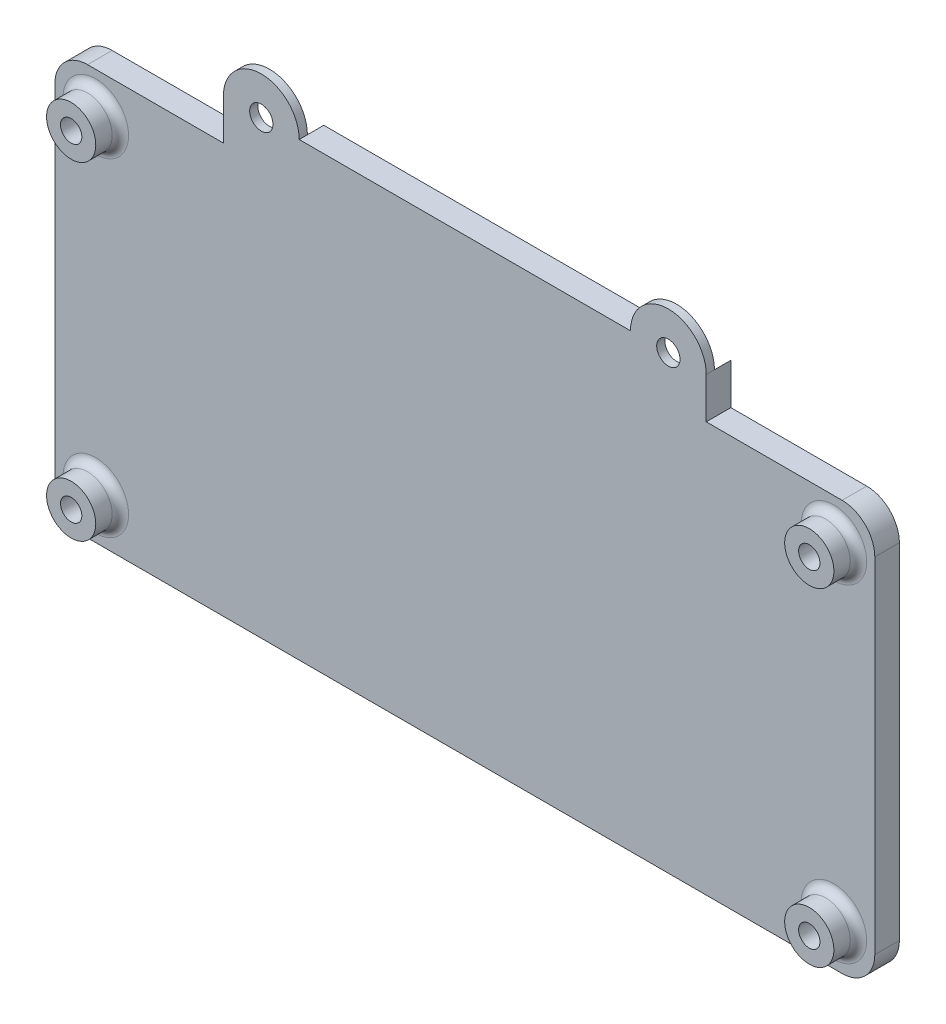
SolidWorks part; units mm, degrees
note: The reader was unsure of these and kept them because the rebuilt part matched: shared geometry of "Sketch1<3>".
ref_plane "Front Plane" through (0, 0, 0) normal (0, 0, 1) x (1, 0, 0)
ref_plane "Top Plane" through (0, 0, 0) normal (0, 1, 0) x (1, 0, 0)
ref_plane "Right Plane" through (0, 0, 0) normal (1, 0, 0) x (0, 0, -1)
sketch "Sketch1" plane through (0, 0, 0) normal (0, 0, 1) x (1, 0, 0)
  line L0 (4, 0.0127) -> (96.0002, 0.0127)
  line L1 (99.9875, 4) -> (99.9875, 46.0001)
  line L2 (96.0002, 49.9874) -> (4, 49.9874)
  line L3 (0.0127, 46.0001) -> (0.0127, 4)
  circle A0 centre (5, 45.0001) radius 1.3
  circle A1 centre (95.0002, 45.0001) radius 1.3
  circle A2 centre (95.0002, 5) radius 1.3
  circle A3 centre (5, 5) radius 1.3
  arc A4 (0.0127, 4) -> (4, 0.0127) centre (4, 4) ccw
  arc A5 (4, 49.9874) -> (0.0127, 46.0001) centre (4, 46.0001) ccw
  arc A6 (96.0002, 49.9874) -> (99.9875, 46.0001) centre (96.0002, 46.0001) cw
  arc A7 (99.9875, 4) -> (96.0002, 0.0127) centre (96.0002, 4) cw
  circle A8 centre (5, 45.0001) radius 3
  circle A9 centre (95.0002, 45.0001) radius 3
  circle A10 centre (5, 5) radius 3
  circle A11 centre (95.0002, 5) radius 3
extrude "Boss-Extrude1" add sketch "Sketch1" along normal blind 3 contours A7 L1 A6 L2 A5 L3 A4 L0 A11 A10 A9 A8
extrude "Boss-Extrude2" add sketch "Sketch1<3>" along normal blind 6 contours A8 A0 | A9 A1 | A11 A2 | A10 A3
sketch "Sketch1<3>" plane through (0, 0, 0) normal (0, 0, 1) x (1, 0, 0) same geometry as "Sketch1"
fillet "Fillet1" radius 1 4 edges at (98.0002, 5, 3) (98.0002, 45.0001, 3) (8, 45.0001, 3) (8, 5, 3)
sketch "Sketch2" plane through (0, 0, 3) normal (0, 0, 1) x (1, 0, 0)
  line L0 (20.5659, 54.9874) -> (20.5895, 61.7526)
  line L1 (20.5895, 61.7526) -> (29.8027, 61.729)
  line L2 (29.8027, 61.729) -> (29.8027, 54.9874)
  line L3 (70.1975, 54.9874) -> (70.1975, 61.729)
  line L4 (70.1975, 61.729) -> (79.4343, 61.729)
  line L5 (79.4343, 61.729) -> (79.4343, 54.9874)
  line L6 (25.1843, 54.9874) -> (74.8159, 54.9874)
  line L7 (20.5659, 54.9874) -> (20.5659, 49.9874)
  line L8 (96.0002, 49.9874) -> (4, 49.9874) construction
  line L9 (20.5659, 49.9874) -> (79.4343, 49.9874)
  line L10 (79.4343, 49.9874) -> (79.4343, 54.9874)
  line L11 (29.8027, 61.729) -> (70.1975, 61.729)
  circle A0 centre (25.1843, 54.9874) radius 1.4224
  circle A1 centre (74.8159, 54.9874) radius 1.4224
  circle A2 centre (74.8159, 54.9874) radius 4.6184
  circle A3 centre (25.1843, 54.9874) radius 4.6184
  point P17 (50.0001, 54.9874)
sketch "Sketch3" plane through (0, 0, 3) normal (0, 0, 1) x (1, 0, 0)
  line L0 (96.0002, 49.9874) -> (4, 49.9874) construction
  line L1 (50.0001, 49.9874) -> (50.0001, 54.9874)
  point P0 (50.0001, 49.9874)
extrude "Boss-Extrude3" add sketch "Sketch2" against normal up to surface (3 mm away)
sketch "Sketch6" plane through (0, 0, 0) normal (0, 0, -1) x (-1, 0, 0)
  circle A0 centre (-74.8159, 54.9874) radius 4.6184
  circle A1 centre (-25.1843, 54.9874) radius 4.6184
extrude "Cut-Extrude1" cut sketch "Sketch6" against normal blind 2
